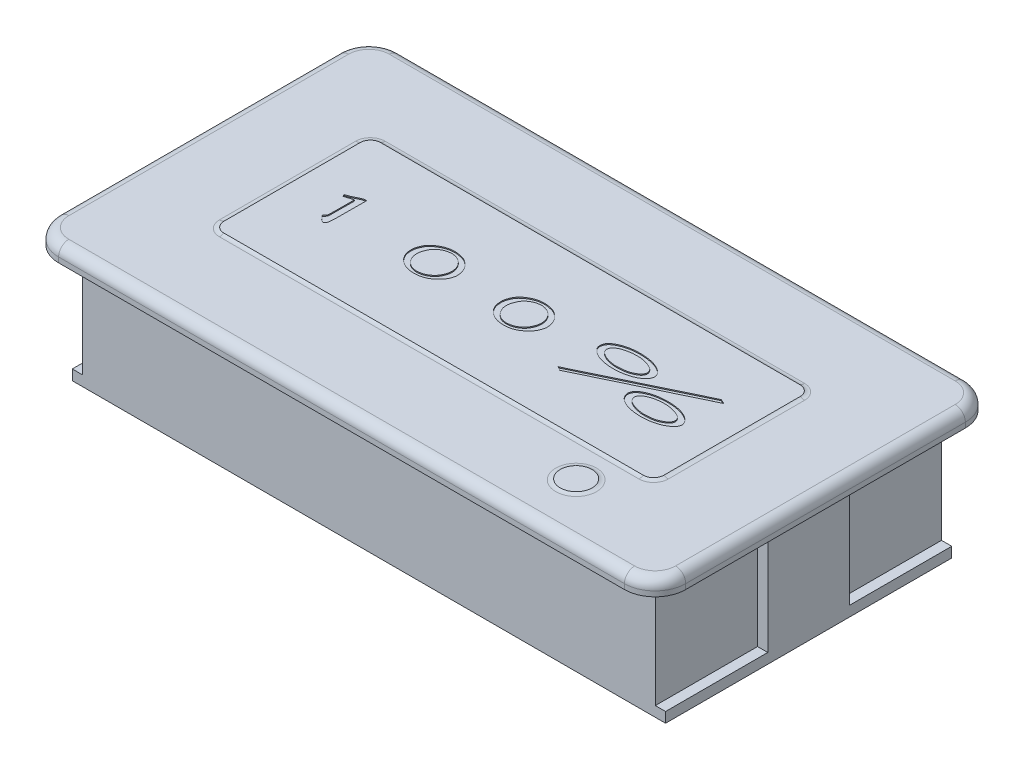
SolidWorks part; units mm, degrees
ref_plane "前视基准面" through (0, 0, 0) normal (0, 0, 1) x (1, 0, 0)
ref_plane "上视基准面" through (0, 0, 0) normal (0, 1, 0) x (1, 0, 0)
ref_plane "右视基准面" through (0, 0, 0) normal (1, 0, 0) x (0, 0, -1)
sketch "草图1" plane through (0, 0, 0) normal (0, 1, 0) x (1, 0, 0)
  line L1 (30.68, -16.68) -> (-30.68, -16.68)
  line L2 (30.68, -16.68) -> (30.68, 16.68)
  line L3 (30.68, 16.68) -> (-30.68, 16.68)
  line L4 (-30.68, -16.68) -> (-30.68, 16.68)
  line L5 (30.68, -16.68) -> (-30.68, 16.68) construction
  line L6 (30.68, 16.68) -> (-30.68, -16.68) construction
  point P0 (0, 0)
  dimension "D1" = 61.36
  dimension "D2" = 33.36
extrude "凸台-拉伸1" add sketch "草图1" along normal blind 1.5
sketch "草图2" plane through (0, 0, 0) normal (0, -1, 0) x (1, 0, 0)
  line L1 (29.025, -14) -> (-29.025, -14)
  line L2 (29.025, -14) -> (29.025, 14)
  line L3 (29.025, 14) -> (-29.025, 14)
  line L4 (-29.025, -14) -> (-29.025, 14)
  line L5 (29.025, -14) -> (-29.025, 14) construction
  line L6 (29.025, 14) -> (-29.025, -14) construction
  point P0 (0, 0)
  dimension "D1" = 28
  dimension "D2" = 58.05
extrude "凸台-拉伸2" add sketch "草图2" along normal blind 12
sketch "草图3" plane through (0, 0, 14) normal (0, 0, 1) x (1, 0, 0)
  line L0 (0, 0) -> (0, -12) construction
  line L1 (-29.025, 0) -> (-28.025, 0)
  line L2 (-29.025, 0) -> (-29.025, -11)
  line L3 (-29.025, -11) -> (-28.025, -11)
  line L4 (-28.025, 0) -> (-28.025, -11)
  line L5 (29.025, -12) -> (-29.025, -12) construction
  line L6 (28.025, 0) -> (28.025, -11)
  line L7 (29.025, -11) -> (28.025, -11)
  line L8 (29.025, 0) -> (29.025, -11)
  line L9 (29.025, 0) -> (28.025, 0)
  dimension "D1" = 1
  dimension "D2" = 1
extrude "切除-拉伸1" cut sketch "草图3" against normal up to next
sketch "草图6" plane through (0, -12, 0) normal (0, -1, 0) x (1, 0, 0)
  line L0 (-29.025, 14) -> (-29.025, -14) construction
  line L1 (-24.025, 12) -> (-16.025, 12)
  line L2 (-24.025, 12) -> (-24.025, 9)
  line L3 (-24.025, 9) -> (-16.025, 9)
  line L4 (-16.025, 12) -> (-16.025, 9)
  line L5 (-24.025, 12) -> (-16.025, 9) construction
  line L6 (-24.025, 9) -> (-16.025, 12) construction
  line L7 (28.025, 14) -> (-28.025, 14) construction
  point P0 (-20.025, 10.5)
  dimension "D1" = 8
  dimension "D2" = 3
  dimension "D3" = 5
  dimension "D4" = 2
extrude "切除-拉伸2" cut sketch "草图6" against normal blind 0.1
sketch "草图8" plane through (0, 1.5, 0) normal (0, 1, 0) x (1, 0, 0)
  line L1 (21.5225, -7.6677) -> (-21.5225, -7.6677)
  line L2 (21.5225, -7.6677) -> (21.5225, 7.6677)
  line L3 (21.5225, 7.6677) -> (-21.5225, 7.6677)
  line L4 (-21.5225, -7.6677) -> (-21.5225, 7.6677)
  line L5 (21.5225, -7.6677) -> (-21.5225, 7.6677) construction
  line L6 (21.5225, 7.6677) -> (-21.5225, -7.6677) construction
  circle A0 centre (17.5253, -11.2482) radius 1.5617
  point P0 (0, 0)
extrude "凸台-拉伸5" add sketch "草图8" along normal blind 0.1
fillet "圆角1" radius 3 4 edges at (-30.68, 0.75, 16.68) (30.68, 0.75, 16.68) (30.68, 0.75, -16.68) (-30.68, 0.75, -16.68)
fillet "圆角2" radius 1 4 edges at (21.5225, 1.55, 7.6677) (-21.5225, 1.55, 7.6677) (21.5225, 1.55, -7.6677) (-21.5225, 1.55, -7.6677)
fillet "圆角3" radius 1 17 edges at (21.2296, 1.5, 7.3748) (21.5225, 1.5, 0) (21.2296, 1.5, -7.3748) (0, 1.5, -7.6677) (-21.2296, 1.5, -7.3748) (-21.5225, 1.5, 0) (-21.2296, 1.5, 7.3748) (0, 1.5, 7.6677) (-29.8013, 1.5, -15.8013) (0, 1.5, -16.68) (29.8013, 1.5, -15.8013) (30.68, 1.5, 0) (29.8013, 1.5, 15.8013) (0, 1.5, 16.68) (-29.8013, 1.5, 15.8013) (-30.68, 1.5, 0) (17.5253, 1.5, 12.8099)
sketch "草图9" plane through (0, 1.6, 0) normal (0, 1, 0) x (1, 0, 0)
  text T0 "<b>100%</b>" font "汉仪长仿宋体" height in points 16
extrude "切除-拉伸3" cut sketch "草图9" against normal blind 0.1
sketch "草图10" plane through (0, -11.9, 0) normal (0, -1, 0) x (1, 0, 0)
  line L0 (-20.025, 12) -> (-20.025, 9) construction
  line L1 (-16.025, 12) -> (-24.025, 12) construction
  line L2 (-24.025, 9) -> (-16.025, 9) construction
  line L3 (-24.025, 12) -> (-24.025, 9) construction
  circle A0 centre (-21.525, 10.5) radius 0.5
  circle A1 centre (-18.525, 10.5) radius 0.5
  point P13 (-24.025, 10.5)
  dimension "D1" = 3
  dimension "D2" = 1
extrude "凸台-拉伸6" add sketch "草图10" along normal blind 0.1
sketch "草图4" plane through (0, 0, 0) normal (0, 0, 1) x (1, 0, 0)
  line L0 (28.025, 0) -> (30, -5.5)
  line L1 (30, -5.5) -> (29.025, -11)
  line L2 (-30.68, 1.5) -> (30.68, 1.5) construction
  line L3 (27.0838, -0.338) -> (28.9689, -5.5875)
  line L4 (28.9689, -5.5875) -> (28.0404, -10.8254)
  arc A0 (28.025, 0) -> (27.0838, -0.338) centre (27.5544, -0.169) ccw
  arc A1 (29.025, -11) -> (28.0404, -10.8254) centre (28.5327, -10.9127) cw
  dimension "D1" = 30
  dimension "D2" = 7
  dimension "D3" = 1
extrude "凸台-拉伸3" [suppressed] add sketch "草图4" along normal mid plane 8
mirror "镜向1" [suppressed] about plane through (0, 0, 0) normal (1, 0, 0)
sketch "草图5" plane through (0, 0, 0) normal (0, 0, 1) x (1, 0, 0)
  line L0 (-27.68, 0) -> (27.68, 0) construction
  line L1 (-29.025, -11) -> (-28.025, -11)
  line L2 (-29.025, -11) -> (-29.025, 0)
  line L3 (-29.025, 0) -> (-28.025, 0)
  line L4 (-28.025, -11) -> (-28.025, 0)
  line L5 (-28.025, -11) -> (-28.025, 0) construction
  line L6 (0, 0) -> (0, -12) construction
  line L7 (29.025, -12) -> (-29.025, -12) construction
  line L8 (28.025, -11) -> (28.025, 0)
  line L9 (29.025, 0) -> (28.025, 0)
  line L10 (29.025, -11) -> (29.025, 0)
  line L11 (29.025, -11) -> (28.025, -11)
extrude "凸台-拉伸4" add sketch "草图5" along normal mid plane 8
